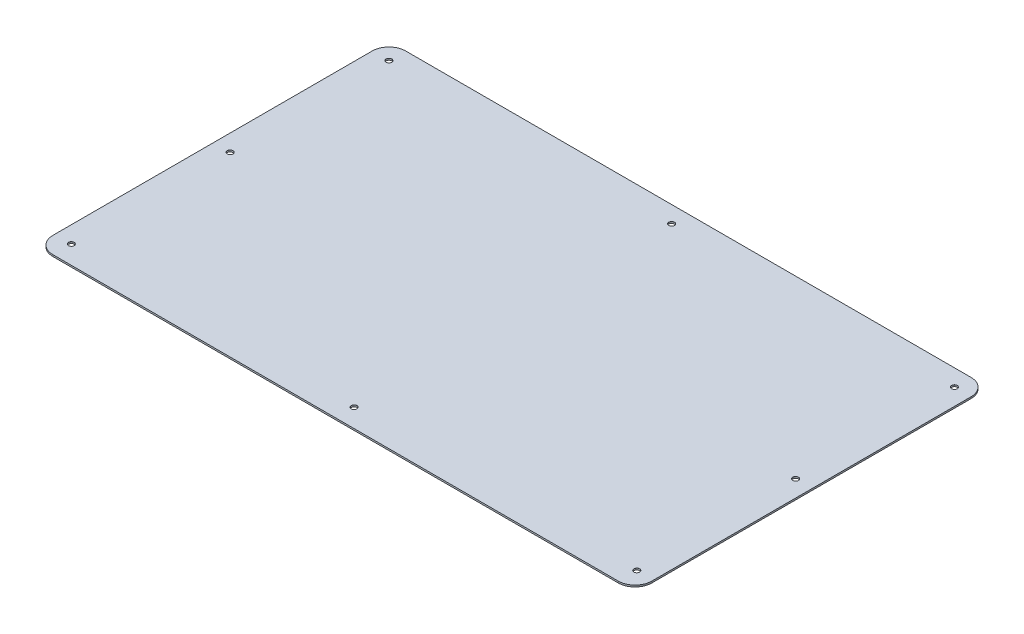
SolidWorks part; units mm, degrees
ref_plane "Front Plane" through (0, 0, 0) normal (0, 0, 1) x (1, 0, 0)
ref_plane "Top Plane" through (0, 0, 0) normal (0, 1, 0) x (1, 0, 0)
ref_plane "Right Plane" through (0, 0, 0) normal (1, 0, 0) x (0, 0, -1)
sketch "Sketch1" plane through (0, 0, 0) normal (0, 1, 0) x (1, 0, 0)
  line L1 (-179.135, 105.525) -> (179.135, 105.525)
  line L2 (-179.135, 105.525) -> (-179.135, -105.525)
  line L3 (-179.135, -105.525) -> (179.135, -105.525)
  line L4 (179.135, 105.525) -> (179.135, -105.525)
  line L5 (-179.135, 105.525) -> (179.135, -105.525) construction
  line L6 (-179.135, -105.525) -> (179.135, 105.525) construction
  point P0 (0, 0)
  dimension "D1" = 358.27
  dimension "D2" = 211.05
extrude "Boss-Extrude1" add sketch "Sketch1" along normal blind 1
fillet "Fillet1" radius 10 4 edges at (-179.135, 0.5, -105.525) (-179.135, 0.5, 105.525) (179.135, 0.5, -105.525) (179.135, 0.5, 105.525)
hole_wizard "M3 Clearance Hole1" positions "Sketch2" profile "Sketch3" hole size "M3" standard "ANSI Metric" end condition through all
sketch "Sketch2" plane through (0, 1, 0) normal (0, 1, 0) x (1, 0, 0)
  point P0 (169.135, 0.525)
  point P3 (169.135, -94.475)
  point P6 (169.135, 95.525)
  point P9 (0, 95.525)
  point P12 (-169.135, 95.525)
  point P15 (-169.135, 0.525)
  point P18 (-169.135, -94.475)
  point P21 (0, -94.475)
sketch "Sketch3" plane through (169.135, 1, -0.525) normal (1, 0, 0) x (0, 0, 1)
  line L0 (0, 0) -> (0, 1)
  line L1 (0, 1) -> (1.7, 1)
  line L2 (1.7, 1) -> (1.7, 0.025)
  line L3 (1.7, 0.025) -> (1.725, 0)
  line L5 (1.725, 0) -> (0, 0)
  line L6 (-1.7, 0.025) -> (-1.725, 0) construction
  line L11 (0, -6.35) -> (0, 107.95) construction
  dimension "Thru Hole Dia." = 3.4
  dimension "Thru Hole Depth" = 1
  dimension "Near C'Sink Dia." = 3.45
  dimension "Near C'Sink Angle" = 90
